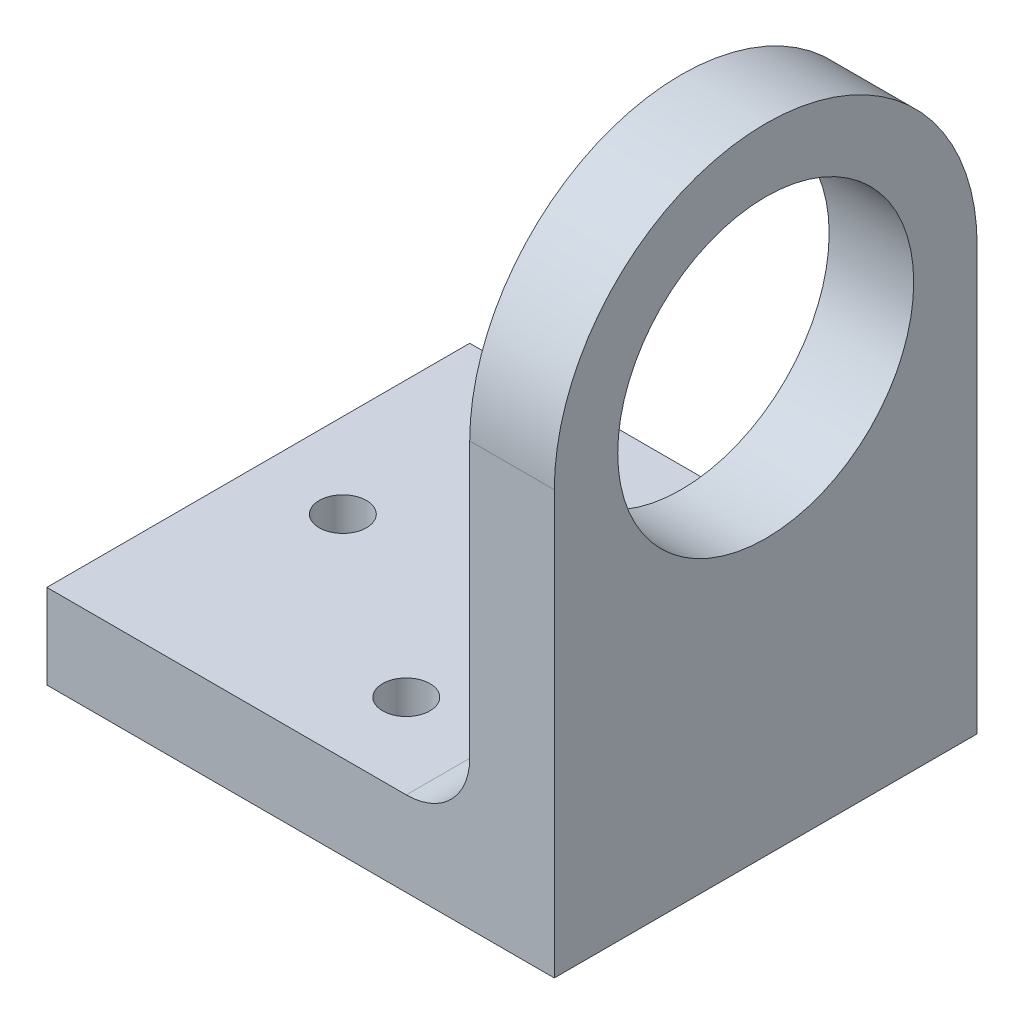
SolidWorks part; units mm, degrees
ref_plane "Front Plane" through (0, 0, 0) normal (0, 0, 1) x (1, 0, 0)
ref_plane "Top Plane" through (0, 0, 0) normal (0, 1, 0) x (1, 0, 0)
ref_plane "Right Plane" through (0, 0, 0) normal (1, 0, 0) x (0, 0, -1)
sketch "Sketch3" plane through (0, 0, 0) normal (1, 0, 0) x (0, 0, -1)
  line L1 (0, 0) -> (31.75, 0)
  line L2 (0, 0) -> (0, 25.4)
  line L4 (31.75, 0) -> (31.75, 25.4)
  circle A4 centre (15.875, 25.4) radius 11.1125
  arc A5 (0, 25.4) -> (31.75, 25.4) centre (15.875, 25.4) cw
  point P34 (15.875, 0)
  dimension "D4" = 22.225
  dimension "D1" = 25.4
  dimension "D2" = 31.75
extrude "Boss-Extrude1" add sketch "Sketch3" along normal blind 6.35
sketch "Sketch5" plane through (6.35, 0, 0) normal (1, 0, 0) x (0, 0, -1)
  line L1 (0, 0) -> (31.75, 0)
  line L2 (0, 0) -> (0, -6.35)
  line L3 (0, -6.35) -> (31.75, -6.35)
  line L4 (31.75, 0) -> (31.75, -6.35)
  dimension "D1" = 6.35
extrude "Boss-Extrude2" add sketch "Sketch5" against normal blind 38.1
fillet "Fillet1" radius 4.7625 1 edges at (0, 0, -15.875)
sketch "Sketch6" plane through (0, 0, 0) normal (0, 1, 0) x (1, 0, 0)
  line L0 (-31.75, 0) -> (-4.7625, 0) construction
  line L1 (-4.7625, 0) -> (-4.7625, 31.75) construction
  line L2 (-31.75, 31.75) -> (-31.75, 0) construction
  line L3 (0, 15.875) -> (-33.0413, 15.875) construction
  line L4 (0, 31.75) -> (0, 0) construction
  circle A0 centre (-11.1125, 6.35) radius 1.777
  circle A2 centre (-25.4, 15.875) radius 1.777
  circle A3 centre (-11.1125, 25.4) radius 1.777
  dimension "D1" = 3.554
  dimension "D2" = 6.35
  dimension "D3" = 6.35
  dimension "D4" = 6.35
extrude "Cut-Extrude1" cut sketch "Sketch6" against normal through all
equation "\"D1@Sketch6\" = 3.3mm + \"normTol\""
equation "\"tightTol\"= 0.005in"
equation "\"normTol\"= 0.01in"
equation "\"looseTol\"= 0.02in"
